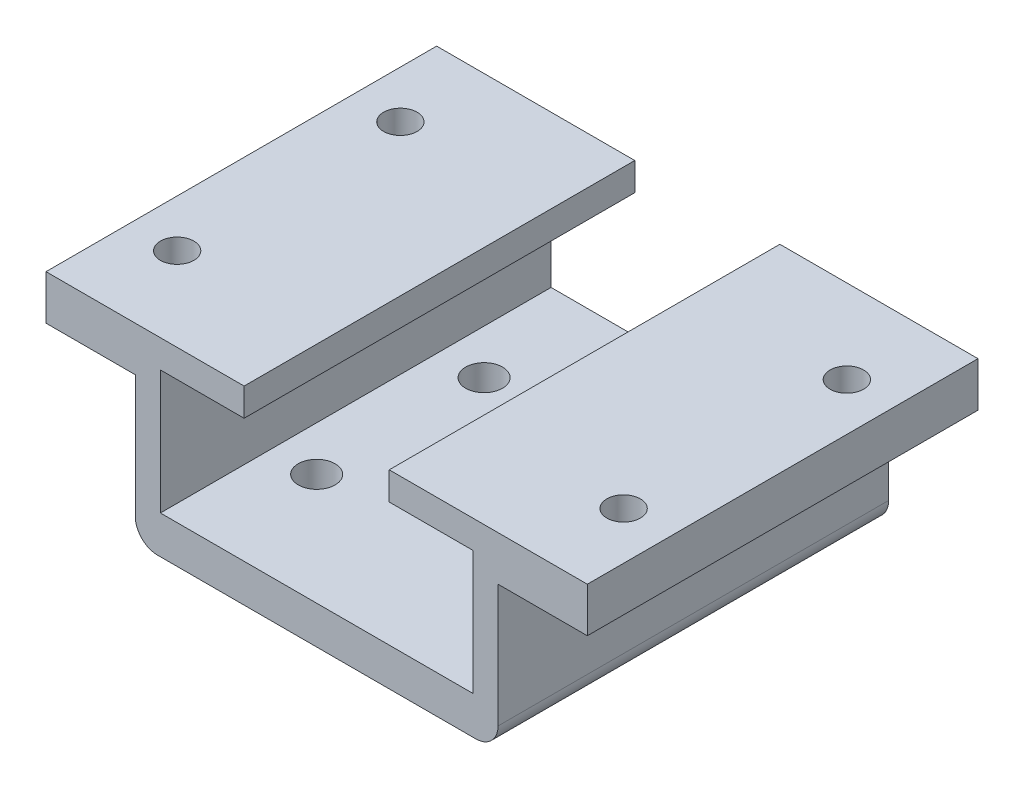
SolidWorks part; units mm, degrees
ref_plane "前视基准面" through (0, 0, 0) normal (0, 0, 1) x (1, 0, 0)
ref_plane "上视基准面" through (0, 0, 0) normal (0, 1, 0) x (1, 0, 0)
ref_plane "右视基准面" through (0, 0, 0) normal (1, 0, 0) x (0, 0, -1)
sketch "草图1" plane through (0, 0, 0) normal (0, 1, 0) x (1, 0, 0)
  line L1 (16.25, -17.5) -> (-16.25, -17.5)
  line L2 (16.25, -17.5) -> (16.25, 17.5)
  line L3 (16.25, 17.5) -> (-16.25, 17.5)
  line L4 (-16.25, -17.5) -> (-16.25, 17.5)
  line L5 (16.25, -17.5) -> (-16.25, 17.5) construction
  line L6 (16.25, 17.5) -> (-16.25, -17.5) construction
  point P0 (0, 0)
  dimension "D1" = 32.5
  dimension "D2" = 35
extrude "凸台-拉伸1" add sketch "草图1" along normal blind 17
sketch "草图2" plane through (0, 0, -17.5) normal (0, 0, -1) x (-1, 0, 0)
  line L0 (-16.25, 17) -> (16.25, 17) construction
  line L1 (-6.5, 14.5) -> (6.5, 14.5)
  line L2 (-6.5, 14.5) -> (-6.5, 17)
  line L3 (-6.5, 17) -> (6.5, 17)
  line L4 (6.5, 14.5) -> (6.5, 17)
  line L5 (-6.5, 14.5) -> (6.5, 17) construction
  line L6 (-6.5, 17) -> (6.5, 14.5) construction
  line L8 (-14, 3.4) -> (14, 3.4)
  line L9 (-14, 3.4) -> (-14, 14.5)
  line L10 (-14, 14.5) -> (14, 14.5)
  line L11 (14, 3.4) -> (14, 14.5)
  line L12 (-14, 3.4) -> (14, 14.5) construction
  line L13 (-14, 14.5) -> (14, 3.4) construction
  point P0 (0, 15.75)
  point P9 (0, 8.95)
  line M7 (16.25, 17) -> (-16.25, 17)
  dimension "D1" = 2.5
  dimension "D2" = 13
  dimension "8" = 28
  dimension "D4" = 13.6
  dimension "D5" = 0
extrude "切除-拉伸2" cut sketch "草图2" against normal through all contours L1 L4 L2 M7 | L8 L11 L10 L1 L9 region at (0, 15.75, -17.5) region at (0, 8.95, -17.5)
sketch "草图4" plane through (0, 0, 0) normal (0, -1, 0) x (1, 0, 0)
  line L1 (-10, -7.5) -> (10, -7.5) construction
  line L2 (-10, -7.5) -> (-10, 7.5) construction
  line L3 (-10, 7.5) -> (10, 7.5) construction
  line L4 (10, -7.5) -> (10, 7.5) construction
  line L5 (-10, -7.5) -> (10, 7.5) construction
  line L6 (-10, 7.5) -> (10, -7.5) construction
  circle A0 centre (-10, 7.5) radius 1.65
  circle A1 centre (10, 7.5) radius 1.65
  circle A2 centre (10, -7.5) radius 1.65
  circle A3 centre (-10, -7.5) radius 1.65
  point P0 (0, 0)
  dimension "D3" = 3.3
  dimension "D4" = 3.3
  dimension "D5" = 3.3
  dimension "D6" = 3.3
  dimension "D1" = 20
  dimension "D2" = 15
extrude "切除-拉伸3" cut sketch "草图4" against normal up to next
fillet "圆角1" radius 2 2 edges at (16.25, 0, 0) (-16.25, 0, 0)
sketch "草图6" plane through (-16.25, 0, 0) normal (-1, 0, 0) x (0, 0, 1)
  line L0 (17.5, 17) -> (17.5, 2) construction
  line L1 (-17.5, 17) -> (17.5, 17)
  line L2 (-17.5, 17) -> (-17.5, 13)
  line L3 (-17.5, 13) -> (17.5, 13)
  line L4 (17.5, 17) -> (17.5, 13)
  dimension "D1" = 4
extrude "凸台-拉伸2" add sketch "草图6" along normal blind 8
mirror "镜向1" about plane through (0, 0, 0) normal (1, 0, 0) of "凸台-拉伸2"
sketch "草图8" plane through (0, 17, 0) normal (0, 1, 0) x (1, 0, 0)
  line L1 (-20, -10) -> (20, -10) construction
  line L2 (-20, -10) -> (-20, 10) construction
  line L3 (-20, 10) -> (20, 10) construction
  line L4 (20, -10) -> (20, 10) construction
  line L5 (-20, -10) -> (20, 10) construction
  line L6 (-20, 10) -> (20, -10) construction
  circle A0 centre (-20, 10) radius 1.5
  circle A1 centre (20, 10) radius 1.5
  circle A2 centre (20, -10) radius 1.5
  circle A3 centre (-20, -10) radius 1.5
  point P0 (0, 0)
  dimension "D3" = 3
  dimension "D4" = 3
  dimension "D5" = 3
  dimension "D6" = 3
  dimension "D1" = 20
  dimension "D2" = 40
extrude "切除-拉伸4" cut sketch "草图8" against normal through all
equation "\"33.5.00mm\"=34"
